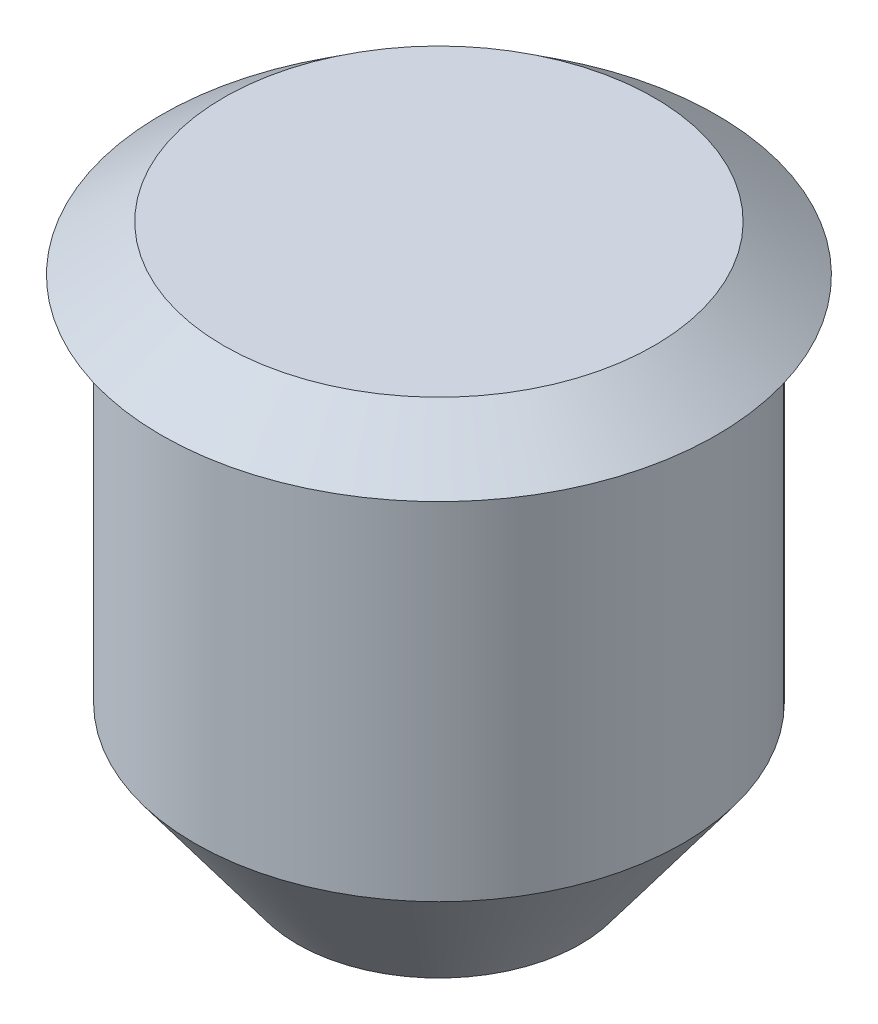
SolidWorks part; units mm, degrees
ref_plane "Front Plane" through (0, 0, 0) normal (0, 0, 1) x (1, 0, 0)
ref_plane "Top Plane" through (0, 0, 0) normal (0, 1, 0) x (1, 0, 0)
ref_plane "Right Plane" through (0, 0, 0) normal (1, 0, 0) x (0, 0, -1)
sketch "Sketch1" plane through (0, 0, 0) normal (1, 0, 0) x (0, 0, -1)
  line L0 (0, 34.1319) -> (0, -16.5783) construction
  line L1 (0, 21.1159) -> (-6.975, 21.1159)
  line L2 (-6.975, 21.1159) -> (-9, 19.6159)
  line L3 (-9, 19.6159) -> (-7.92, 19.6159)
  line L4 (-7.92, 19.6159) -> (-7.92, 7.6159)
  line L5 (-7.92, 7.6159) -> (-4.5867, 3.1159)
  line L6 (-4.5867, 3.1159) -> (0, 3.1159)
  line L7 (0, 21.1159) -> (0, 3.1159)
  point P5 (-7.92, 20.3756)
  point P11 (-7.1013, 20.4653)
  point P12 (-6.1102, 3.1159)
  point P13 (-7.92, 4.5632)
  dimension "D1" = 18
  dimension "D2" = 15.84
  dimension "D3" = 18
  dimension "D4" = 13.95
  dimension "D5" = 1.5
  dimension "D6" = 12
revolve "Revolve1" add sketch "Sketch1" angle 360 about L0
